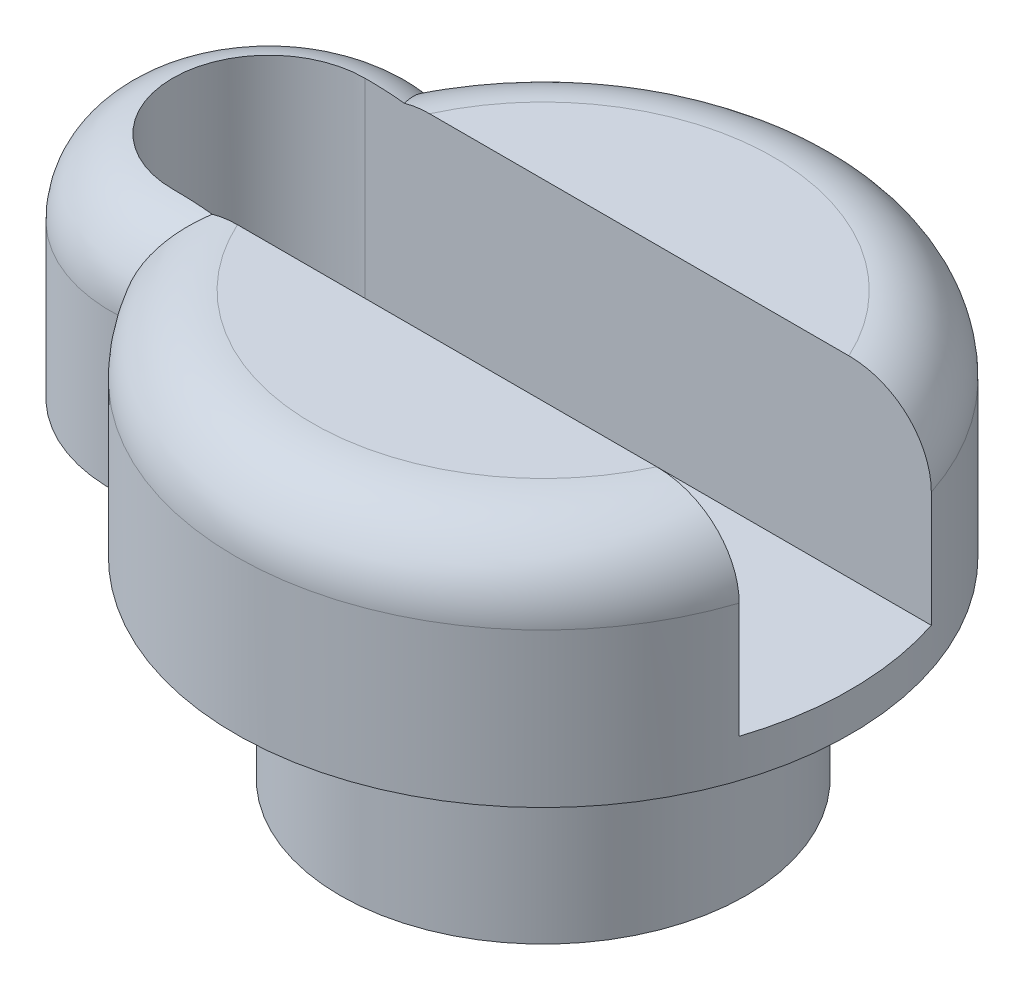
SolidWorks part; units mm, degrees
ref_plane "Front Plane" through (0, 0, 0) normal (0, 0, 1) x (1, 0, 0)
ref_plane "Top Plane" through (0, 0, 0) normal (0, 1, 0) x (1, 0, 0)
ref_plane "Right Plane" through (0, 0, 0) normal (1, 0, 0) x (0, 0, -1)
sketch "Sketch1" plane through (0, 0, 0) normal (0, 1, 0) x (1, 0, 0)
  circle A0 centre (0, 0) radius 2.4638
  circle A1 centre (0, 0) radius 3.3528
  dimension "D1" = 4.9276
  dimension "D2" = 6.7056
extrude "Boss-Extrude1" add sketch "Sketch1" along normal blind 3.175
sketch "Sketch2" plane through (0, 3.175, 0) normal (0, 1, 0) x (1, 0, 0)
  circle A0 centre (0, 0) radius 5.08
  dimension "D1" = 10.16
extrude "Boss-Extrude2" add sketch "Sketch2" along normal blind 3.81
sketch "Sketch3" plane through (0, 6.985, 0) normal (0, 1, 0) x (1, 0, 0)
  line L0 (0, 0) -> (25.4, 0)
  line L1 (0, 0) -> (-4.5337, 0)
  line L2 (0, -1.905) -> (0, 1.905)
  line L3 (0, 1.905) -> (25.4, 0)
  line L4 (0, -1.905) -> (25.4, 0)
  line L5 (-4.5337, 1.5875) -> (4.8256, 1.5875)
  line L6 (-4.5337, -1.5875) -> (4.8256, -1.5875)
  circle A0 centre (0, 0) radius 5.08 construction
  circle A1 centre (0, 0) radius 5.08
  circle A2 centre (-4.5337, 0) radius 1.5875
  circle A3 centre (-4.5337, 0) radius 2.6035
  point P7 (0, 0)
  circle M8 centre (0, 0) radius 5.08
  dimension "D4" = 3.175
  dimension "D1" = 25.4
  dimension "D2" = 1.016
  dimension "D3" = 3.81
extrude "Boss-Extrude3" add sketch "Sketch3" against normal up to surface (3.81 mm away) contours A1 A3 A2 M8 region at (-4.6832, 6.985, -2.1159) up to face at (0, 3.175, 3.3528)
sketch "Sketch4" plane through (0, 6.985, 0) normal (0, 1, 0) x (1, 0, 0)
  line L0 (-4.5337, -1.5875) -> (4.8256, -1.5875) construction
  line L1 (-4.5337, 1.5875) -> (4.8256, 1.5875) construction
  line L2 (-4.5337, -1.5875) -> (4.8256, -1.5875)
  line L3 (-4.5337, 1.5875) -> (4.8256, 1.5875)
  circle A0 centre (-4.5337, 0) radius 1.5875 construction
  circle A1 centre (0, 0) radius 5.08 construction
  arc A2 (-4.5337, 1.5875) -> (-4.5337, -1.5875) centre (-4.5337, 0) ccw
  circle A3 centre (0, 0) radius 5.08
  arc M2 (-4.835, 1.5586) -> (-4.835, -1.5586) centre (0, 0) ccw
  arc M3 (-4.3654, -2.5981) -> (-4.3654, 2.5981) centre (0, 0) ccw
extrude "Cut-Extrude1" cut sketch "Sketch4" against normal blind 3.175 contours L3 A2 L2 M2 M3 region at (0.0008, 6.985, 0)
fillet "Fillet1" radius 1.27 3 edges at (-7.1372, 6.985, 0) (0.5552, 6.985, -5.0496) (0.5552, 6.985, 5.0496)
